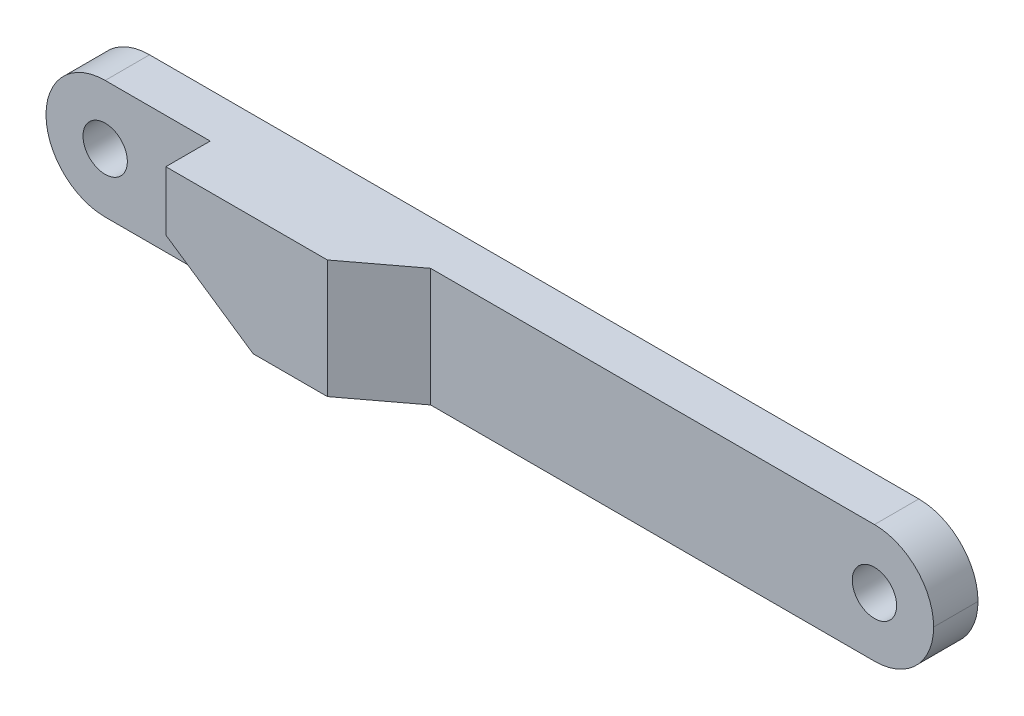
SolidWorks part; units mm, degrees
ref_plane "Płaszczyzna przednia" through (0, 0, 0) normal (0, 0, 1) x (1, 0, 0)
ref_plane "Płaszczyzna górna" through (0, 0, 0) normal (0, 1, 0) x (1, 0, 0)
ref_plane "Płaszczyzna prawa" through (0, 0, 0) normal (1, 0, 0) x (0, 0, -1)
sketch "Szkic1" plane through (0, 0, 0) normal (0, 0, 1) x (1, 0, 0)
  line L1 (0, 0) -> (60, 0)
  line L2 (0, 0) -> (0, 8)
  line L3 (0, 8) -> (60, 8)
  line L4 (60, 0) -> (60, 8)
extrude "Dodanie-wyciągnięcie1" add sketch "Szkic1" along normal blind 3
fillet "Zaokrąglenie1" radius 4 4 edges at (60, 0, 1.5) (60, 8, 1.5) (0, 8, 1.5) (0, 0, 1.5)
sketch "Szkic2" plane through (0, 0, 3) normal (0, 0, 1) x (1, 0, 0)
  circle A0 centre (4, 4) radius 1.5
  circle A1 centre (56, 4) radius 1.5
extrude "Wytnij-wyciągnięcie1" cut sketch "Szkic2" against normal blind 3
sketch "Szkic3" plane through (0, 0, 3) normal (0, 0, 1) x (1, 0, 0)
  line L0 (5.2, 8) -> (17, 0)
  line L1 (56, 8) -> (4, 8) construction
  line L2 (4, 0) -> (56, 0) construction
  line L3 (17, 0) -> (22, 0)
  line L4 (22, 0) -> (22, 8)
  line L5 (22, 8) -> (5.2, 8)
  point P6 (0, 0)
extrude "Dodanie-wyciągnięcie2" add sketch "Szkic3" along normal blind 3
chamfer "Sfazowanie1" distance 4 angle 37 1 edges at (22, 4, 3) first distance on face at (57.5, 4, 3)
sketch "Szkic4" plane through (0, 0, 6) normal (0, 0, 1) x (1, 0, 0)
  line L0 (5.2, 8) -> (11.1, 4)
  line L1 (5.2, 8) -> (17, 0) construction
  line L2 (11.1, 4) -> (11.1, 8)
  line L3 (22.0189, 8) -> (5.2, 8) construction
  line L4 (11.1, 8) -> (5.2, 8)
  point P5 (0, 0)
  point P9 (0, 0)
  point P10 (0, 0)
extrude "Wytnij-wyciągnięcie2" cut sketch "Szkic4" against normal blind 3
